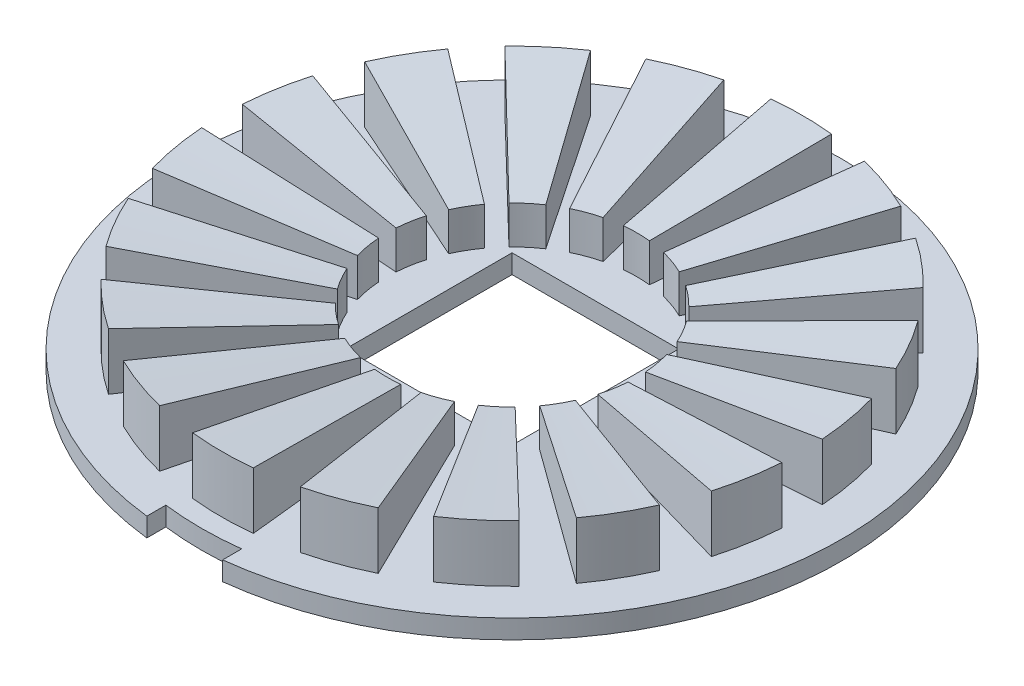
SolidWorks part; units mm, degrees
ref_plane "Front Plane" through (0, 0, 0) normal (0, 0, 1) x (1, 0, 0)
ref_plane "Top Plane" through (0, 0, 0) normal (0, 1, 0) x (1, 0, 0)
ref_plane "Right Plane" through (0, 0, 0) normal (1, 0, 0) x (0, 0, -1)
ref_plane "Plane2" through (0, 1, 0) normal (0, 1, 0) x (1, 0, 0)
ref_plane "Plane1" through (0, 4, 0) normal (0, 1, 0) x (1, 0, 0)
ref_plane "Plane3" through (0, 3, 0) normal (0, 1, 0) x (1, 0, 0)
sketch "Sketch5" plane through (0, 0, 0) normal (0, 1, 0) x (-1, 0, 0)
  line L1 (-4.4, 4.4) -> (4.4, 4.4)
  line L2 (-4.4, 4.4) -> (-4.4, -4.4)
  line L3 (-4.4, -4.4) -> (4.4, -4.4)
  line L4 (4.4, 4.4) -> (4.4, -4.4)
  line L5 (-4.4, 4.4) -> (4.4, -4.4) construction
  line L6 (-4.4, -4.4) -> (4.4, 4.4) construction
  point P0 (0, 0)
  dimension "D1" = 8.8
sketch "Sketch8" plane through (0, 0, 0) normal (0, 1, 0) x (1, 0, 0)
  line L2 (-1.9012, -17.3964) -> (-1.9012, -16.3901) construction
  line L3 (1.9012, -17.3964) -> (1.9012, -16.3901) construction
  line L4 (-2.0012, -17.2845) -> (-2.0012, -16.2775)
  line L5 (2.0012, -17.2845) -> (2.0012, -16.2775)
  arc A2 (-1.9012, -16.3901) -> (1.9012, -16.3901) centre (0, 0) ccw construction
  arc A3 (1.9012, -17.3964) -> (-1.9012, -17.3964) centre (0, 0) ccw construction
  circle A4 centre (0, 0) radius 17.5 construction
  arc A5 (-2.0012, -16.2775) -> (2.0012, -16.2775) centre (0, 0) ccw
  arc A6 (2.0012, -17.2845) -> (-2.0012, -17.2845) centre (0, 0) ccw
  circle A7 centre (0, 0) radius 15.35 construction
  dimension "D1" = 35
  dimension "D3" = 2.05
  dimension "D2" = 0.1
sketch "Sketch6" plane through (0, 3, 0) normal (0, 1, 0) x (1, 0, 0)
  circle A0 centre (0, 0) radius 6.6 construction
  dimension "D1" = 13.2
sketch "Sketch3" plane through (0, 1, 0) normal (0, 1, 0) x (1, 0, 0)
  line L0 (0, 15.4) -> (0, 0) construction
  line L1 (0, 0) -> (0.6899, 6.5638) construction
  line L2 (-1.6045, 15.2659) -> (-0.6899, 6.5638)
  line L3 (-0.6899, 6.5638) -> (0, 0) construction
  line L4 (0.6899, 6.5638) -> (1.6045, 15.2659)
  line L5 (3.7135, 14.894) -> (1.5967, 6.404)
  line L6 (2.8932, 5.932) -> (6.729, 13.7965)
  line L7 (8.5836, 12.7257) -> (3.6907, 5.4716)
  line L8 (4.7476, 4.5847) -> (11.0419, 10.663)
  line L9 (12.4184, 9.0225) -> (5.3395, 3.8794)
  line L10 (6.0294, 2.6845) -> (14.0229, 6.2434)
  line L11 (14.7554, 4.231) -> (6.3443, 1.8192)
  line L12 (6.5839, 0.4604) -> (15.3126, 1.0708)
  line L13 (15.3126, -1.0708) -> (6.5839, -0.4604)
  line L14 (6.3443, -1.8192) -> (14.7554, -4.231)
  line L15 (14.0229, -6.2434) -> (6.0294, -2.6845)
  line L16 (5.3395, -3.8794) -> (12.4184, -9.0225)
  line L17 (11.0419, -10.663) -> (4.7476, -4.5847)
  line L18 (3.6907, -5.4716) -> (8.5836, -12.7257)
  line L19 (6.729, -13.7965) -> (2.8932, -5.932)
  line L20 (1.5967, -6.404) -> (3.7135, -14.894)
  line L21 (1.6045, -15.2659) -> (0.6899, -6.5638)
  line L22 (-0.6899, -6.5638) -> (-1.6045, -15.2659)
  line L23 (-3.7135, -14.894) -> (-1.5967, -6.404)
  line L24 (-2.8932, -5.932) -> (-6.729, -13.7965)
  line L25 (-8.5836, -12.7257) -> (-3.6907, -5.4716)
  line L26 (-4.7476, -4.5847) -> (-11.0419, -10.663)
  line L27 (-12.4184, -9.0225) -> (-5.3395, -3.8794)
  line L28 (-6.0294, -2.6845) -> (-14.0229, -6.2434)
  line L29 (-14.7554, -4.231) -> (-6.3443, -1.8192)
  line L30 (-6.5839, -0.4604) -> (-15.3126, -1.0708)
  line L31 (-15.3126, 1.0708) -> (-6.5839, 0.4604)
  line L32 (-6.3443, 1.8192) -> (-14.7554, 4.231)
  line L33 (-14.0229, 6.2434) -> (-6.0294, 2.6845)
  line L34 (-5.3395, 3.8794) -> (-12.4184, 9.0225)
  line L35 (-11.0419, 10.663) -> (-4.7476, 4.5847)
  line L36 (-3.6907, 5.4716) -> (-8.5836, 12.7257)
  line L37 (-6.729, 13.7965) -> (-2.8932, 5.932)
  line L38 (-1.5967, 6.404) -> (-3.7135, 14.894)
  circle A1 centre (0, 0) radius 15.35 construction
  arc A2 (0.6899, 6.5638) -> (-0.6899, 6.5638) centre (0, 0) ccw
  arc A3 (1.6045, 15.2659) -> (-1.6045, 15.2659) centre (0, 0) ccw
  arc A4 (2.8932, 5.932) -> (1.5967, 6.404) centre (0, 0) ccw
  arc A5 (6.729, 13.7965) -> (3.7135, 14.894) centre (0, 0) ccw
  arc A6 (4.7476, 4.5847) -> (3.6907, 5.4716) centre (0, 0) ccw
  arc A7 (11.0419, 10.663) -> (8.5836, 12.7257) centre (0, 0) ccw
  arc A8 (6.0294, 2.6845) -> (5.3395, 3.8794) centre (0, 0) ccw
  arc A9 (14.0229, 6.2434) -> (12.4184, 9.0225) centre (0, 0) ccw
  arc A10 (6.5839, 0.4604) -> (6.3443, 1.8192) centre (0, 0) ccw
  arc A11 (15.3126, 1.0708) -> (14.7554, 4.231) centre (0, 0) ccw
  arc A12 (6.3443, -1.8192) -> (6.5839, -0.4604) centre (0, 0) ccw
  arc A13 (14.7554, -4.231) -> (15.3126, -1.0708) centre (0, 0) ccw
  arc A14 (5.3395, -3.8794) -> (6.0294, -2.6845) centre (0, 0) ccw
  arc A15 (12.4184, -9.0225) -> (14.0229, -6.2434) centre (0, 0) ccw
  arc A16 (3.6907, -5.4716) -> (4.7476, -4.5847) centre (0, 0) ccw
  arc A17 (8.5836, -12.7257) -> (11.0419, -10.663) centre (0, 0) ccw
  arc A18 (1.5967, -6.404) -> (2.8932, -5.932) centre (0, 0) ccw
  arc A19 (3.7135, -14.894) -> (6.729, -13.7965) centre (0, 0) ccw
  arc A20 (-0.6899, -6.5638) -> (0.6899, -6.5638) centre (0, 0) ccw
  arc A21 (-1.6045, -15.2659) -> (1.6045, -15.2659) centre (0, 0) ccw
  arc A22 (-2.8932, -5.932) -> (-1.5967, -6.404) centre (0, 0) ccw
  arc A23 (-6.729, -13.7965) -> (-3.7135, -14.894) centre (0, 0) ccw
  arc A24 (-4.7476, -4.5847) -> (-3.6907, -5.4716) centre (0, 0) ccw
  arc A25 (-11.0419, -10.663) -> (-8.5836, -12.7257) centre (0, 0) ccw
  arc A26 (-6.0294, -2.6845) -> (-5.3395, -3.8794) centre (0, 0) ccw
  arc A27 (-14.0229, -6.2434) -> (-12.4184, -9.0225) centre (0, 0) ccw
  arc A28 (-6.5839, -0.4604) -> (-6.3443, -1.8192) centre (0, 0) ccw
  arc A29 (-15.3126, -1.0708) -> (-14.7554, -4.231) centre (0, 0) ccw
  arc A30 (-6.3443, 1.8192) -> (-6.5839, 0.4604) centre (0, 0) ccw
  arc A31 (-14.7554, 4.231) -> (-15.3126, 1.0708) centre (0, 0) ccw
  arc A32 (-5.3395, 3.8794) -> (-6.0294, 2.6845) centre (0, 0) ccw
  arc A33 (-12.4184, 9.0225) -> (-14.0229, 6.2434) centre (0, 0) ccw
  arc A34 (-3.6907, 5.4716) -> (-4.7476, 4.5847) centre (0, 0) ccw
  arc A35 (-8.5836, 12.7257) -> (-11.0419, 10.663) centre (0, 0) ccw
  arc A36 (-1.5967, 6.404) -> (-2.8932, 5.932) centre (0, 0) ccw
  arc A37 (-3.7135, 14.894) -> (-6.729, 13.7965) centre (0, 0) ccw
  circle A39 centre (0, 0) radius 6.6 construction
  point P2 (0, 0)
  point P8 (0, 0)
  point P10 (0, 0)
  point P82 (0, 0)
  point P83 (0, 0)
  point P84 (0, 0)
  dimension "D1" = 12
  dimension "D2" = 6
  dimension "D3" = 18
extrude "Boss-Extrude6" add sketch "Sketch8" along normal up to surface (1 mm away) up to plane "Plane2"
extrude "Cut-Extrude3" cut sketch "Sketch5" along normal up to surface (1 mm away) up to plane "Plane2"
extrude "Boss-Extrude7" add sketch "Sketch3" along normal up to surface (3 mm away) up to plane "Plane1"
sketch "Sketch7" plane through (0, 0, 0) normal (0, 0, 1) x (1, 0, 0)
  line L0 (6.5, 3) -> (15.35, 4)
  line L1 (6.6, 3) -> (-6.6, 3) construction
  line L2 (15.35, 4) -> (6.5, 4)
  line L3 (6.5, 4) -> (6.5, 3)
  line L7 (6.5839, 4) -> (15.3126, 4) construction
  line L8 (15.35, 0) -> (15.35, 6.5718) construction
  point P4 (0, 0)
ref_axis "Axis1" through (0, 3, 0) along (0, 1, 0)
revolve "Cut-Revolve2" cut sketch "Sketch7" angle 360 about axis through (0, 3, 0) along (0, 1, 0) region at (9.45, 3.6667, 0)
